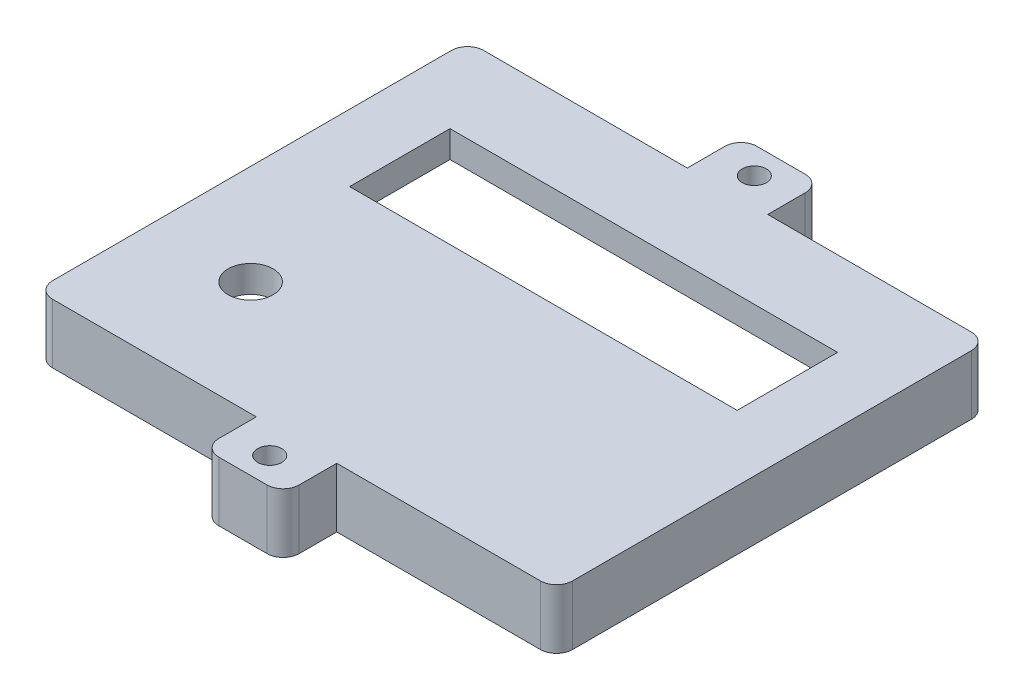
SolidWorks part; units mm, degrees
ref_plane "Front Plane" through (0, 0, 0) normal (0, 0, 1) x (1, 0, 0)
ref_plane "Top Plane" through (0, 0, 0) normal (0, 1, 0) x (1, 0, 0)
ref_plane "Right Plane" through (0, 0, 0) normal (1, 0, 0) x (0, 0, -1)
sketch "Sketch1" plane through (0, 0, 0) normal (0, 1, 0) x (1, 0, 0)
  line L1 (-45.0661, 38.3957) -> (51.9339, 38.3957)
  line L2 (-45.0661, 38.3957) -> (-45.0661, -42.0055)
  line L3 (-45.0661, -42.0055) -> (51.9339, -42.0055)
  line L4 (51.9339, 38.3957) -> (51.9339, -42.0055)
extrude "Boss-Extrude1" add sketch "Sketch1" along normal blind 12.6
sketch "Sketch2" plane through (0, 12.6, 0) normal (0, 1, 0) x (1, 0, 0)
  line L0 (39.2339, 22.1316) -> (-32.0661, 22.1316) construction
  line L1 (-32.5661, 22.6316) -> (39.7339, 22.6316)
  line L2 (-32.5661, 22.6316) -> (-32.5661, 3.8965)
  line L3 (-32.5661, 3.8965) -> (39.7339, 3.8965)
  line L4 (39.7339, 22.6316) -> (39.7339, 3.8965)
  line L5 (-32.0661, 4.3965) -> (39.2339, 4.3965) construction
  line L6 (-32.0661, 22.1316) -> (-32.0661, 4.3965) construction
  line L7 (39.2339, 4.3965) -> (39.2339, 22.1316) construction
  line L8 (-32.5661, -26.8684) -> (-20.2661, -14.5684) construction
  circle A0 centre (-26.4161, -20.7184) radius 4.2
  dimension "D5" = 8.4
  dimension "D1" = 0.5
  dimension "D2" = 0.5
  dimension "D3" = 0.5
  dimension "D4" = 0.5
extrude "Cut-Extrude1" cut sketch "Sketch2" against normal up to next
sketch "Sketch3" plane through (0, 12.6, 0) normal (0, 1, 0) x (1, 0, 0)
  line L4 (-41.3661, 31.8316) -> (-41.3661, -34.1684)
  line L5 (-39.8661, -35.6684) -> (46.1339, -35.6684)
  line L6 (47.6339, -34.1684) -> (47.6339, 31.8316)
  line L7 (46.1339, 33.3316) -> (-39.8661, 33.3316)
  arc A4 (-41.3661, -34.1684) -> (-39.8661, -35.6684) centre (-39.8661, -34.1684) ccw
  arc A5 (46.1339, -35.6684) -> (47.6339, -34.1684) centre (46.1339, -34.1684) ccw
  arc A6 (47.6339, 31.8316) -> (46.1339, 33.3316) centre (46.1339, 31.8316) ccw
  arc A7 (-39.8661, 33.3316) -> (-41.3661, 31.8316) centre (-39.8661, 31.8316) ccw
extrude "Cut-Extrude2" cut sketch "Sketch3" against normal blind 10 from offset 5 offset against normal yes
sketch "Sketch6" plane through (0, 0, 0) normal (0, -1, 0) x (1, 0, 0)
  line L5 (51.9339, -38.3957) -> (-45.0661, -38.3957)
  line L6 (51.9339, -38.3957) -> (51.9339, 42.0055)
  line L7 (51.9339, 42.0055) -> (-45.0661, 42.0055)
  line L8 (-39.8661, -34.5316) -> (46.1339, -34.5316)
  line L9 (-42.5661, 34.1684) -> (-42.5661, -31.8316)
  line L10 (46.1339, 36.8684) -> (-39.8661, 36.8684)
  line L11 (48.8339, -31.8316) -> (48.8339, 34.1684)
  line L12 (-39.8661, -34.5316) -> (46.1339, -34.5316)
  line L13 (-42.5661, 34.1684) -> (-42.5661, -31.8316)
  line L14 (46.1339, 36.8684) -> (-39.8661, 36.8684)
  line L15 (48.8339, -31.8316) -> (48.8339, 34.1684)
  line L16 (-45.0661, -38.3957) -> (-45.0661, 42.0055)
  arc A8 (-42.5661, -31.8316) -> (-39.8661, -34.5316) centre (-39.8661, -31.8316) ccw
  arc A9 (-39.8661, 36.8684) -> (-42.5661, 34.1684) centre (-39.8661, 34.1684) ccw
  arc A10 (48.8339, 34.1684) -> (46.1339, 36.8684) centre (46.1339, 34.1684) ccw
  arc A11 (46.1339, -34.5316) -> (48.8339, -31.8316) centre (46.1339, -31.8316) ccw
  arc A12 (-42.5661, -31.8316) -> (-39.8661, -34.5316) centre (-39.8661, -31.8316) ccw
  arc A13 (-39.8661, 36.8684) -> (-42.5661, 34.1684) centre (-39.8661, 34.1684) ccw
  arc A14 (48.8339, 34.1684) -> (46.1339, 36.8684) centre (46.1339, 34.1684) ccw
  arc A15 (46.1339, -34.5316) -> (48.8339, -31.8316) centre (46.1339, -31.8316) ccw
  dimension "D1" = 1.2
extrude "Cut-Extrude3" cut sketch "Sketch6" against normal blind 1.5
fillet "Fillet1" radius 3 4 edges at (51.9339, 7.05, -38.3957) (-45.0661, 7.05, -38.3957) (-45.0661, 7.05, 42.0055) (51.9339, 7.05, 42.0055)
sketch "Sketch7" plane through (0, 0, 42.0055) normal (0, 0, 1) x (1, 0, 0)
  line L0 (3.4339, 1.5) -> (3.4339, 12.6) construction
  line L3 (48.9339, 1.5) -> (-42.0661, 1.5) construction
  line L4 (-42.0661, 12.6) -> (48.9339, 12.6) construction
  line L6 (-4.0661, 12.6) -> (10.9339, 12.6)
  line L7 (-4.0661, 12.6) -> (-4.0661, 1.5)
  line L8 (-4.0661, 1.5) -> (10.9339, 1.5)
  line L9 (10.9339, 12.6) -> (10.9339, 1.5)
  line L10 (-4.0661, 12.6) -> (10.9339, 1.5) construction
  line L11 (-4.0661, 1.5) -> (10.9339, 12.6) construction
  point P6 (3.4339, 7.05)
  dimension "D1" = 15
extrude "Boss-Extrude2" add sketch "Sketch7" along normal blind 10
fillet "Fillet2" radius 3 2 edges at (10.9339, 7.05, 52.0055) (-4.0661, 7.05, 52.0055)
sketch "Sketch8" plane through (0, 0, -38.3957) normal (0, 0, -1) x (-1, 0, 0)
  line L0 (-3.4339, 1.5) -> (-3.4339, 12.6) construction
  line L1 (42.0661, 1.5) -> (-48.9339, 1.5) construction
  line L2 (-48.9339, 12.6) -> (42.0661, 12.6) construction
  line L4 (-10.9339, 12.6) -> (4.0661, 12.6)
  line L5 (-10.9339, 12.6) -> (-10.9339, 1.5)
  line L6 (-10.9339, 1.5) -> (4.0661, 1.5)
  line L7 (4.0661, 12.6) -> (4.0661, 1.5)
  line L8 (-10.9339, 12.6) -> (4.0661, 1.5) construction
  line L9 (-10.9339, 1.5) -> (4.0661, 12.6) construction
  point P6 (-3.4339, 7.05)
  dimension "D1" = 15
extrude "Boss-Extrude3" add sketch "Sketch8" along normal blind 10
fillet "Fillet3" radius 3 2 edges at (10.9339, 7.05, -48.3957) (-4.0661, 7.05, -48.3957)
sketch "Sketch9" plane through (0, 12.6, 0) normal (0, 1, 0) x (1, 0, 0)
  line L0 (3.4339, 48.3957) -> (3.4339, -52.0055) construction
  line L1 (-1.0661, 48.3957) -> (7.9339, 48.3957) construction
  line L2 (7.9339, -52.0055) -> (-1.0661, -52.0055) construction
  circle A0 centre (3.4339, 43.3957) radius 2.25
  circle A1 centre (3.4339, -47.0055) radius 2.25
  dimension "D3" = 4.5
  dimension "D4" = 4.5
  dimension "D1" = 5
  dimension "D2" = 5
extrude "Cut-Extrude4" cut sketch "Sketch9" against normal up to next
sketch "Sketch10" plane through (0, 0, 0) normal (0, 1, 0) x (1, 0, 0)
  line L5 (-32.5661, 3.8965) -> (39.7339, 3.8965)
  line L6 (39.7339, 3.8965) -> (39.7339, 22.6316)
  line L7 (39.7339, 22.6316) -> (-32.5661, 22.6316)
  line L8 (-32.5661, 22.6316) -> (-32.5661, 3.8965)
  line L9 (-32.5661, 3.8965) -> (39.7339, 3.8965)
  line L10 (39.7339, 3.8965) -> (39.7339, 22.6316)
  line L11 (39.7339, 22.6316) -> (-32.5661, 22.6316)
  line L12 (7.9339, 48.3957) -> (-1.0661, 48.3957)
  line L13 (10.9339, 38.3957) -> (10.9339, 45.3957)
  line L14 (48.9339, 38.3957) -> (10.9339, 38.3957)
  line L15 (51.9339, -39.0055) -> (51.9339, 35.3957)
  line L16 (10.9339, -42.0055) -> (48.9339, -42.0055)
  line L17 (10.9339, -49.0055) -> (10.9339, -42.0055)
  line L18 (-1.0661, -52.0055) -> (7.9339, -52.0055)
  line L19 (-4.0661, -42.0055) -> (-4.0661, -49.0055)
  line L20 (-42.0661, -42.0055) -> (-4.0661, -42.0055)
  line L21 (-45.0661, 35.3957) -> (-45.0661, -39.0055)
  line L22 (-4.0661, 38.3957) -> (-42.0661, 38.3957)
  line L23 (-4.0661, 45.3957) -> (-4.0661, 38.3957)
  line L24 (7.9339, 48.3957) -> (-1.0661, 48.3957)
  line L25 (10.9339, 38.3957) -> (10.9339, 45.3957)
  line L26 (48.9339, 38.3957) -> (10.9339, 38.3957)
  line L27 (51.9339, -39.0055) -> (51.9339, 35.3957)
  line L28 (10.9339, -42.0055) -> (48.9339, -42.0055)
  line L29 (10.9339, -49.0055) -> (10.9339, -42.0055)
  line L30 (-1.0661, -52.0055) -> (7.9339, -52.0055)
  line L31 (-4.0661, -42.0055) -> (-4.0661, -49.0055)
  line L32 (-42.0661, -42.0055) -> (-4.0661, -42.0055)
  line L33 (-45.0661, 35.3957) -> (-45.0661, -39.0055)
  line L34 (-4.0661, 38.3957) -> (-42.0661, 38.3957)
  line L35 (-4.0661, 45.3957) -> (-4.0661, 38.3957)
  line L36 (-32.5661, 22.6316) -> (-32.5661, 3.8965)
  line L38 (-42.5661, 31.8316) -> (-42.5661, -34.1684)
  line L39 (-39.8661, -36.8684) -> (46.1339, -36.8684)
  line L40 (48.8339, -34.1684) -> (48.8339, 31.8316)
  line L41 (46.1339, 34.5316) -> (-39.8661, 34.5316)
  line L42 (-42.5661, 31.8316) -> (-42.5661, -34.1684)
  line L43 (-39.8661, -36.8684) -> (46.1339, -36.8684)
  line L44 (48.8339, -34.1684) -> (48.8339, 31.8316)
  line L45 (46.1339, 34.5316) -> (-39.8661, 34.5316)
  line L46 (46.1339, 33.3316) -> (-39.8661, 33.3316)
  line L47 (-41.3661, 31.8316) -> (-41.3661, -34.1684)
  line L48 (-39.8661, -35.6684) -> (46.1339, -35.6684)
  line L49 (47.6339, -34.1684) -> (47.6339, 31.8316)
  line L50 (46.1339, 33.3316) -> (-39.8661, 33.3316)
  line L51 (-41.3661, 31.8316) -> (-41.3661, -34.1684)
  line L52 (-39.8661, -35.6684) -> (46.1339, -35.6684)
  line L53 (47.6339, -34.1684) -> (47.6339, 31.8316)
  circle A0 centre (3.4339, -47.0055) radius 2.25 construction
  circle A1 centre (-26.4161, -20.7184) radius 4.2 construction
  circle A2 centre (3.4339, 43.3957) radius 2.25 construction
  circle A3 centre (3.4339, -47.0055) radius 2.25
  circle A4 centre (-26.4161, -20.7184) radius 4.2
  circle A5 centre (3.4339, 43.3957) radius 2.25
  arc A8 (10.9339, 45.3957) -> (7.9339, 48.3957) centre (7.9339, 45.3957) ccw
  arc A9 (51.9339, 35.3957) -> (48.9339, 38.3957) centre (48.9339, 35.3957) ccw
  arc A10 (48.9339, -42.0055) -> (51.9339, -39.0055) centre (48.9339, -39.0055) ccw
  arc A11 (7.9339, -52.0055) -> (10.9339, -49.0055) centre (7.9339, -49.0055) ccw
  arc A12 (-4.0661, -49.0055) -> (-1.0661, -52.0055) centre (-1.0661, -49.0055) ccw
  arc A13 (-45.0661, -39.0055) -> (-42.0661, -42.0055) centre (-42.0661, -39.0055) ccw
  arc A14 (-42.0661, 38.3957) -> (-45.0661, 35.3957) centre (-42.0661, 35.3957) ccw
  arc A15 (-1.0661, 48.3957) -> (-4.0661, 45.3957) centre (-1.0661, 45.3957) ccw
  arc A16 (10.9339, 45.3957) -> (7.9339, 48.3957) centre (7.9339, 45.3957) ccw
  arc A17 (51.9339, 35.3957) -> (48.9339, 38.3957) centre (48.9339, 35.3957) ccw
  arc A18 (48.9339, -42.0055) -> (51.9339, -39.0055) centre (48.9339, -39.0055) ccw
  arc A19 (7.9339, -52.0055) -> (10.9339, -49.0055) centre (7.9339, -49.0055) ccw
  arc A20 (-4.0661, -49.0055) -> (-1.0661, -52.0055) centre (-1.0661, -49.0055) ccw
  arc A21 (-45.0661, -39.0055) -> (-42.0661, -42.0055) centre (-42.0661, -39.0055) ccw
  arc A22 (-42.0661, 38.3957) -> (-45.0661, 35.3957) centre (-42.0661, 35.3957) ccw
  arc A23 (-1.0661, 48.3957) -> (-4.0661, 45.3957) centre (-1.0661, 45.3957) ccw
  arc A26 (-42.5661, -34.1684) -> (-39.8661, -36.8684) centre (-39.8661, -34.1684) ccw
  arc A27 (46.1339, -36.8684) -> (48.8339, -34.1684) centre (46.1339, -34.1684) ccw
  arc A28 (48.8339, 31.8316) -> (46.1339, 34.5316) centre (46.1339, 31.8316) ccw
  arc A29 (-39.8661, 34.5316) -> (-42.5661, 31.8316) centre (-39.8661, 31.8316) ccw
  arc A30 (-42.5661, -34.1684) -> (-39.8661, -36.8684) centre (-39.8661, -34.1684) ccw
  arc A31 (46.1339, -36.8684) -> (48.8339, -34.1684) centre (46.1339, -34.1684) ccw
  arc A32 (48.8339, 31.8316) -> (46.1339, 34.5316) centre (46.1339, 31.8316) ccw
  arc A33 (-39.8661, 34.5316) -> (-42.5661, 31.8316) centre (-39.8661, 31.8316) ccw
  arc A34 (-39.8661, 33.3316) -> (-41.3661, 31.8316) centre (-39.8661, 31.8316) ccw
  arc A35 (-41.3661, -34.1684) -> (-39.8661, -35.6684) centre (-39.8661, -34.1684) ccw
  arc A36 (46.1339, -35.6684) -> (47.6339, -34.1684) centre (46.1339, -34.1684) ccw
  arc A37 (47.6339, 31.8316) -> (46.1339, 33.3316) centre (46.1339, 31.8316) ccw
  arc A38 (-39.8661, 33.3316) -> (-41.3661, 31.8316) centre (-39.8661, 31.8316) ccw
  arc A39 (-41.3661, -34.1684) -> (-39.8661, -35.6684) centre (-39.8661, -34.1684) ccw
  arc A40 (46.1339, -35.6684) -> (47.6339, -34.1684) centre (46.1339, -34.1684) ccw
  arc A41 (47.6339, 31.8316) -> (46.1339, 33.3316) centre (46.1339, 31.8316) ccw
  dimension "D1" = 0
  dimension "D2" = 0
  dimension "D3" = 0
  dimension "D4" = 0
